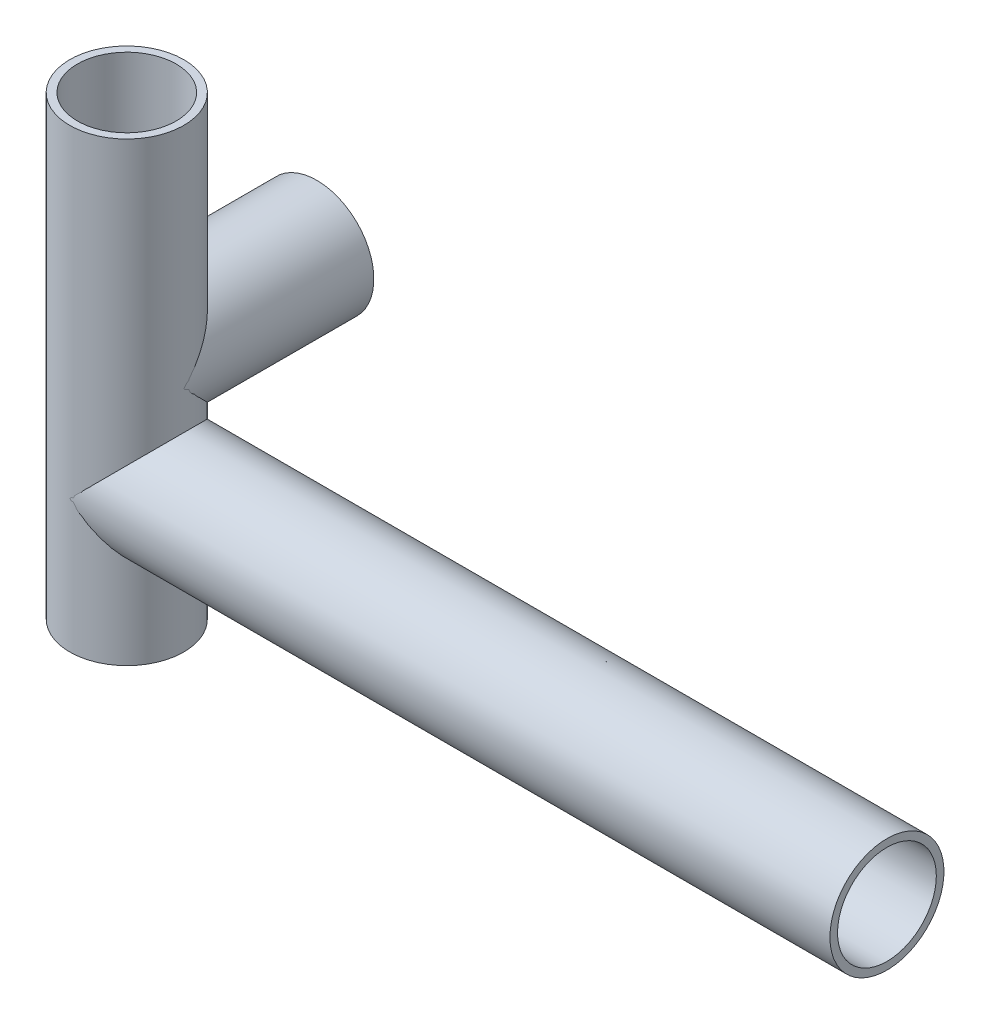
SolidWorks part; units mm, degrees
ref_plane "Front Plane" through (0, 0, 0) normal (0, 0, 1) x (1, 0, 0)
ref_plane "Top Plane" through (0, 0, 0) normal (0, 1, 0) x (1, 0, 0)
ref_plane "Right Plane" through (0, 0, 0) normal (1, 0, 0) x (0, 0, -1)
sketch "Sketch1" plane through (0, 0, 0) normal (1, 0, 0) x (0, 0, -1)
  line L1 (0, 118.3216) -> (0, -1.6784)
  dimension "D2" = 120
sweep "Sweep-Thin6" add path "Sketch1" circular profile diameter 30 parameters "D1"=2, "D3"=30
sketch "Sketch66" plane through (0, 0, 0) normal (1, 0, 0) x (0, 0, -1)
  line L0 (0, 118.3216) -> (0, -1.6784) construction
  line L1 (0, 118.3216) -> (0, -1.6784)
  line L2 (0, 58.3216) -> (50, 58.3216)
  dimension "D1" = 50
sweep "Sweep-Thin8" add path "Sketch66" circular profile diameter 30 parameters "D1"=2, "D3"=30
sketch "Sketch135" plane through (0, 118.3216, 0) normal (0, 1, 0) x (1, 0, 0)
  circle A1 centre (0, 0) radius 15
  circle A2 centre (0, 0) radius 15
  dimension "D1" = 0
extrude "Cut-Extrude1" cut sketch "Sketch135" against normal blind 185
sketch "Sketch142" plane through (0, 0, 0) normal (0, 0, 1) x (1, 0, 0)
  line L0 (0, 58.3216) -> (0, 33.3216)
  line L1 (0, 33.3216) -> (200, 33.3216)
  point P3 (0, 27.8971)
  dimension "D1" = 200
  dimension "D2" = 25
sweep "Sweep-Thin9" add path "Sketch142" circular profile diameter 30 parameters "D1"=2, "D3"=30
sketch "Sketch183" plane through (0, 118.3216, 0) normal (0, 1, 0) x (1, 0, 0)
  circle A0 centre (0, 0) radius 15 construction
  circle A1 centre (0, 0) radius 15
extrude "Cut-Extrude2" cut sketch "Sketch183" against normal through all
